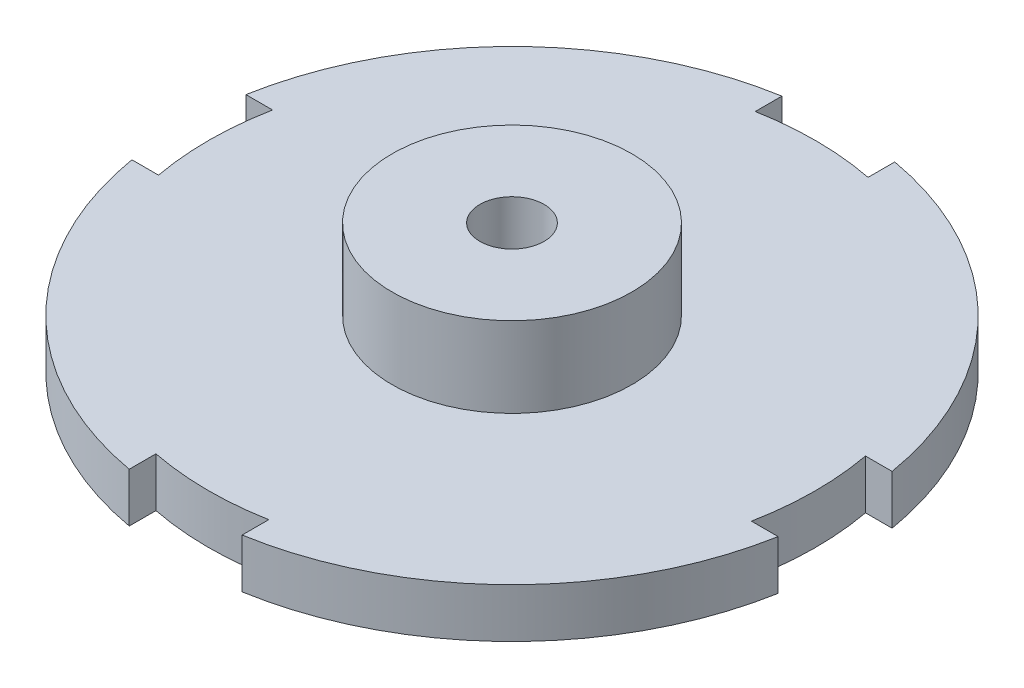
SolidWorks part; units mm, degrees
ref_plane "Front Plane" through (0, 0, 0) normal (0, 0, 1) x (1, 0, 0)
ref_plane "Top Plane" through (0, 0, 0) normal (0, 1, 0) x (1, 0, 0)
ref_plane "Right Plane" through (0, 0, 0) normal (1, 0, 0) x (0, 0, -1)
sketch "Sketch1" plane through (0, 0, 0) normal (0, 1, 0) x (1, 0, 0)
  line L0 (35.4054, 6.5405) -> (38.5653, 6.5405)
  line L1 (35.3329, -6.9215) -> (38.4988, -6.9215)
  line L2 (-55, 0) -> (55, 0) construction
  line L3 (6.5405, -35.4054) -> (6.5405, -38.5653)
  line L4 (-6.9215, -35.3329) -> (-6.9215, -38.4988)
  line L5 (-35.4054, -6.5405) -> (-38.5653, -6.5405)
  line L6 (-35.3329, 6.9215) -> (-38.4988, 6.9215)
  line L7 (-6.5405, 35.4054) -> (-6.5405, 38.5653)
  line L8 (6.9215, 35.3329) -> (6.9215, 38.4988)
  arc A1 (-38.5653, -6.5405) -> (-6.9215, -38.4988) centre (0, 0) ccw
  circle A2 centre (0, 0) radius 3.81
  arc A3 (-35.3329, 6.9215) -> (-35.4054, -6.5405) centre (0, 0) ccw
  arc A4 (6.9215, 35.3329) -> (-6.5405, 35.4054) centre (0, 0) ccw
  arc A5 (35.3329, -6.9215) -> (35.4054, 6.5405) centre (0, 0) ccw
  arc A6 (-6.9215, -35.3329) -> (6.5405, -35.4054) centre (0, 0) ccw
  arc A7 (6.5405, -38.5653) -> (38.4988, -6.9215) centre (0, 0) ccw
  arc A8 (38.5653, 6.5405) -> (6.9215, 38.4988) centre (0, 0) ccw
  arc A9 (-6.5405, 38.5653) -> (-38.4988, 6.9215) centre (0, 0) ccw
  point P26 (0, 0)
  dimension "D1" = 78.232
  dimension "D2" = 72.009
  dimension "D6" = 7.62
  dimension "D3" = 13.462
  dimension "D4" = 6.5405
  dimension "D5" = 4
ref_axis "Axis1" through (41.0751, 0, 0) along (-1, 0, 0)
ref_plane "Plane2" through (0, 0, 0) normal (0, -0.9903, 0.1392) x (-1, 0, 0)
ref_plane "Plane3" through (0, 6.2882, -0.8837) normal (0, -0.9903, 0.1392) x (-1, 0, 0)
extrude "Boss-Extrude2" add sketch "Sketch1" along normal blind 5.842
sketch "Sketch2" plane through (0, 0, 0) normal (0, -1, 0) x (1, 0, 0)
  line L3 (17.3777, -10.033) -> (-0.2866, -40.6283)
  line L4 (-4.5397, -40.3749) -> (8.1962, -18.3157)
  line L5 (3.2131, 0) -> (-3.2131, 0) construction
  arc A3 (8.1962, -18.3157) -> (17.3777, -10.033) centre (0, 0) cw
  arc A4 (-0.2866, -40.6283) -> (-4.5397, -40.3749) centre (0, 0) cw
  point P4 (8.5456, -25.3307)
  dimension "D1" = 20.066
  dimension "D2" = 3.81
  dimension "D3" = 60
extrude "Cut-Extrude1" cut sketch "Sketch2" against normal blind 3.81
sketch "Sketch3" plane through (0, 0, 0) normal (0, -1, 0) x (1, 0, 0)
  circle A0 centre (0, 0) radius 31.75
extrude "Cut-Extrude2" cut sketch "Sketch3" against normal blind 1.27
sketch "Sketch4" plane through (0, 5.842, 0) normal (0, 1, 0) x (1, 0, 0)
  circle A0 centre (0, 0) radius 14.224
  circle M17 centre (0, 0) radius 3.81
extrude "Boss-Extrude3" add sketch "Sketch4" along normal blind 9.525 contours A0 M17 region at (-13.8217, 5.842, 0)
